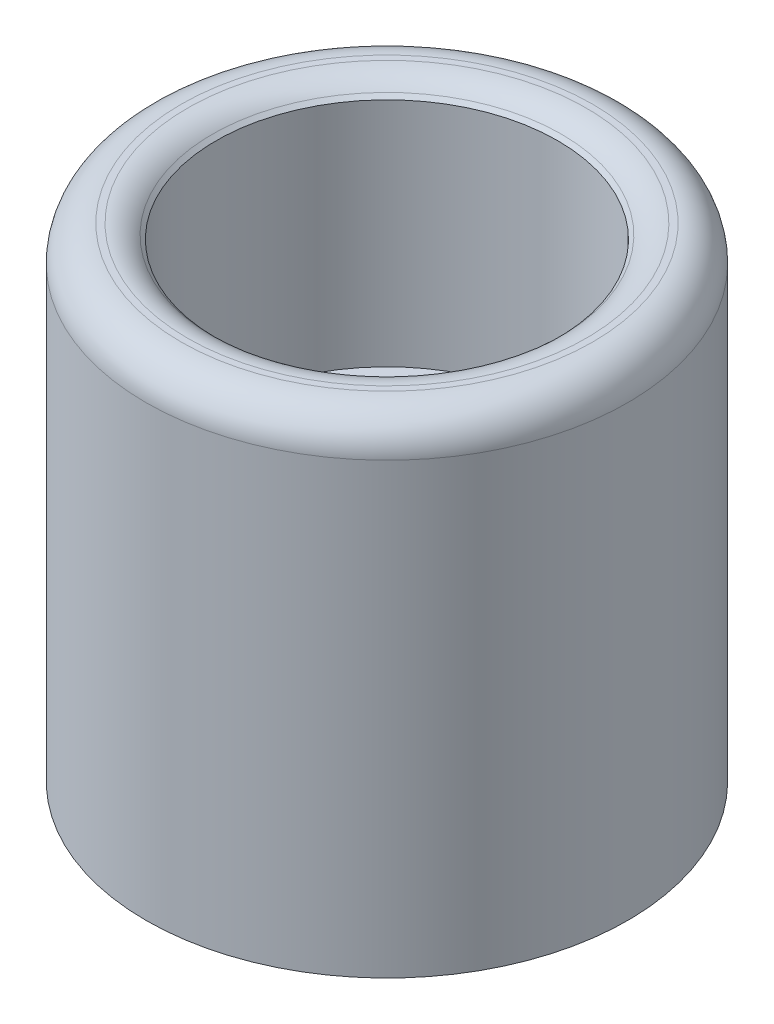
SolidWorks part; units mm, degrees
ref_plane "Front Plane" through (0, 0, 0) normal (0, 0, 1) x (1, 0, 0)
ref_plane "Top Plane" through (0, 0, 0) normal (0, 1, 0) x (1, 0, 0)
ref_plane "Right Plane" through (0, 0, 0) normal (1, 0, 0) x (0, 0, -1)
sketch "Sketch1" plane through (0, 0, 0) normal (0, 1, 0) x (1, 0, 0)
  circle A0 centre (0, 0) radius 24.384
  circle A1 centre (0, 0) radius 34.384
  dimension "D1" = 48.768
  dimension "D2" = 10
extrude "Boss-Extrude1" add sketch "Sketch1" along normal blind 35
extrude "Boss-Extrude2" add sketch "Sketch1<3>" against normal blind 34 contours A1 A0 | A0 region at (-33.4115, 0, 0)
sketch "Sketch1<3>" plane through (0, 0, 0) normal (0, 1, 0) x (1, 0, 0) same geometry as "Sketch1"
sketch "Sketch3" plane through (0, 0, 0) normal (0, 1, 0) x (1, 0, 0)
  circle A0 centre (0, 0) radius 12.5
  dimension "D1" = 25
chamfer "Chamfer1" distance 2 angle 45 1 edges at (0, 35, 24.384)
fillet "Fillet2" radius 5 2 edges at (0, 35, 34.384) (0, 35, 26.384)
ref_plane "Plane1" through (0, -22, 0) normal (0, -1, 0) x (-1, 0, 0)
sketch "Sketch10" plane through (0, -22, 0) normal (0, -1, 0) x (-1, 0, 0)
  line L1 (7.3323, 0) -> (3.6662, 6.35)
  line L2 (3.6662, 6.35) -> (-3.6662, 6.35)
  line L3 (-3.6662, 6.35) -> (-7.3323, 0)
  line L4 (-7.3323, 0) -> (-3.6662, -6.35)
  line L5 (-3.6662, -6.35) -> (3.6662, -6.35)
  line L6 (3.6662, -6.35) -> (7.3323, 0)
  circle A0 centre (0, 0) radius 6.35 construction
  dimension "D1" = 12.7
extrude "Cut-Extrude1" cut sketch "Sketch10" against normal blind 3.5719 and the other way blind 3.5719
hole_wizard "Ø10.0mm Dowel Hole1" positions "Sketch13" profile "Sketch14" hole size "Ø10.0" standard "ANSI Metric" end condition through all
sketch "Sketch13" plane through (0, -34, 0) normal (0, -1, 0) x (-1, 0, 0)
  point P0 (0, 0)
sketch "Sketch14" plane through (0, -34, 0) normal (1, 0, 0) x (0, 0, -1)
  line L0 (0, 0) -> (0, 69)
  line L1 (0, 69) -> (5, 69)
  line L2 (5, 69) -> (5, 0)
  line L5 (5, 0) -> (0, 0)
  line L11 (0, -6.35) -> (0, 107.95) construction
  dimension "Thru Hole Dia." = 10
  dimension "Thru Hole Depth" = 69
